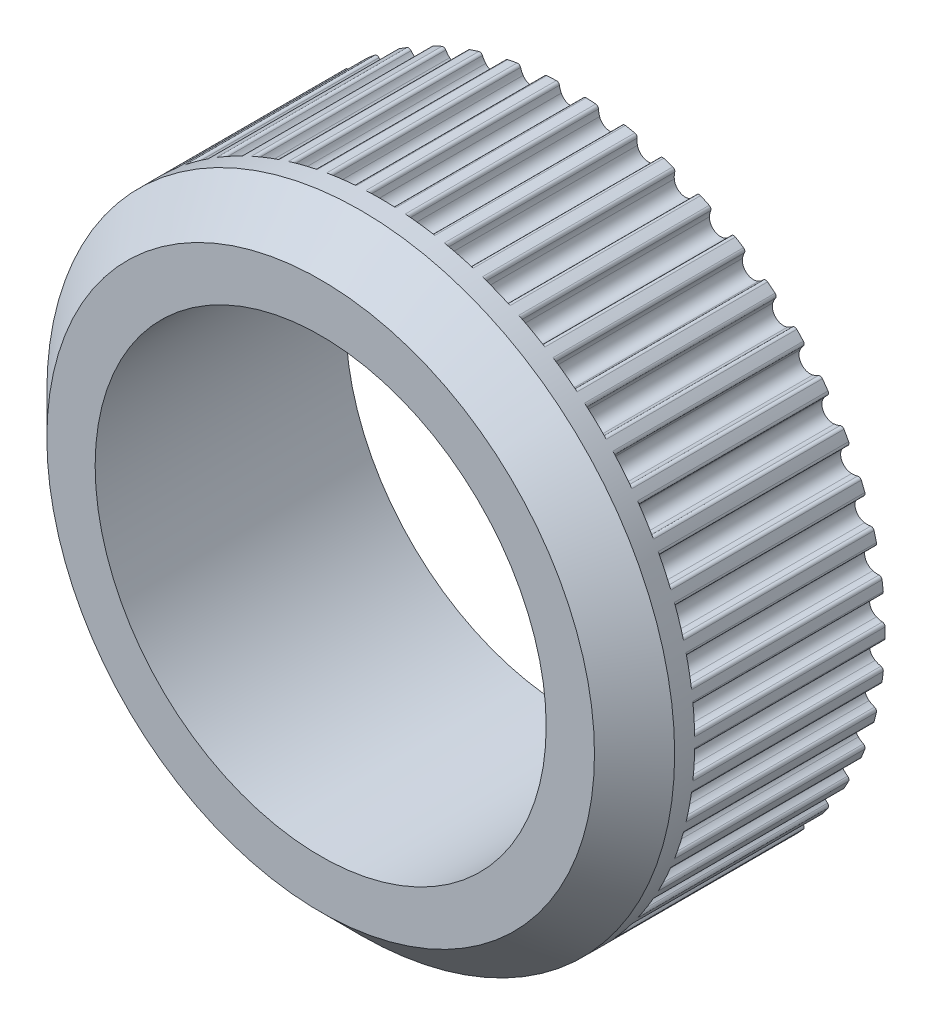
SolidWorks part; units mm, degrees
ref_plane "Front Plane" through (0, 0, 0) normal (0, 0, 1) x (1, 0, 0)
ref_plane "Top Plane" through (0, 0, 0) normal (0, 1, 0) x (1, 0, 0)
ref_plane "Right Plane" through (0, 0, 0) normal (1, 0, 0) x (0, 0, -1)
sketch "Sketch1" plane through (0, 0, 0) normal (0, 0, 1) x (1, 0, 0)
  line L1 (-1.885, 14.909) -> (1.885, 14.909) construction
  line L4 (0, 0) -> (0, 14.909) construction
  line L5 (0, 14.909) -> (0, 17.5781) construction
  line L6 (0, 15.913) -> (1.996, 15.7873) construction
  line L7 (1.996, 15.7873) -> (2.8744, 15.6763) construction
  line L8 (1.996, 15.7873) -> (1.885, 14.909) construction
  line L9 (-1.996, 15.7873) -> (-1.885, 14.909) construction
  line L10 (-1.9642, 15.5353) -> (-2.3604, 18.669)
  line L11 (-2.3604, 18.669) -> (2.3604, 18.669)
  line L12 (2.3604, 18.669) -> (1.9642, 15.5353)
  circle A0 centre (0, 0) radius 15.913 construction
  circle A1 centre (0, 0) radius 18.669 construction
  circle A2 centre (0, 0) radius 15.659 construction
  arc A3 (-0.4989, 15.2208) -> (0.4989, 15.2208) centre (0, 15.464) ccw
  arc A4 (-0.4989, 15.2208) -> (-0.5893, 15.5133) centre (0.4, 15.659) cw
  arc A5 (-1.9642, 15.5353) -> (-0.7449, 15.6413) centre (0, 0) cw
  arc A6 (-0.5893, 15.5133) -> (-0.7449, 15.6413) centre (-0.7377, 15.4914) ccw
  arc A7 (1.9642, 15.5353) -> (0.7449, 15.6413) centre (0, 0) ccw
  arc A8 (0.5893, 15.5133) -> (0.7449, 15.6413) centre (0.7377, 15.4914) cw
  arc A9 (0.4989, 15.2208) -> (0.5893, 15.5133) centre (-0.4, 15.659) ccw
  point P6 (0, 20.9083)
  point P11 (0, 15.913)
  point P13 (0, 18.669)
  point P14 (0, 15.659)
  dimension "D1" = 3.3302
  dimension "PD" = 31.826
  dimension "D2" = 1.6651
  dimension "OD" = 37.338
  dimension "R3" = 0.555
  dimension "R2" = 1
  dimension "R1" = 0.15
  dimension "b" = 0.4
  dimension "D3" = 2
  dimension "PLD" = 0.254
  dimension "h" = 0.75
sketch "Sketch2" plane through (0, 0, 0) normal (1, 0, 0) x (0, 0, -1)
  line L0 (-0.3687, 11.25) -> (9.1313, 11.25)
  line L3 (-0.3687, 11.25) -> (-0.3687, 18.669)
  line L4 (-0.3687, 18.669) -> (0.6963, 18.669) construction
  line L5 (0.6963, 18.669) -> (0.6963, 15.659) construction
  line L6 (0.6963, 15.659) -> (8.0663, 15.659)
  line L7 (8.0663, 15.659) -> (8.0663, 18.669) construction
  line L8 (8.0663, 18.669) -> (9.1313, 18.669) construction
  line L9 (9.1313, 18.669) -> (9.1313, 11.25)
  line L10 (-9.1313, 0) -> (9.1313, 0) construction
  line L11 (8.5988, 18.669) -> (8.0663, 17.164)
  line L12 (0.6963, 17.164) -> (0.1638, 18.669)
  line L13 (-0.3687, 18.669) -> (0.1638, 18.669)
  line L14 (0.6963, 17.164) -> (0.6963, 15.659)
  line L15 (8.0663, 15.659) -> (8.0663, 17.164)
  line L16 (8.5988, 18.669) -> (9.1313, 18.669)
  point P12 (0.6963, 17.164)
  point P14 (0.1638, 18.669)
  point P20 (8.0663, 17.164)
  point P21 (8.5988, 18.669)
  point P25 (8.0663, 0)
  point P26 (0.6963, 0)
  dimension "OA" = 18.2626
  dimension "Bore" = 22.5
  dimension "Outside Width" = 9.5
  dimension "Inside Width" = 7.37
revolve "Revolve1" add sketch "Sketch2" angle 360 mid plane about L10
sketch "Sketch3" plane through (0, 0, 0) normal (0, 0, 1) x (1, 0, 0)
  line L6 (2.3604, 18.669) -> (-2.3604, 18.669)
  line L7 (1.9642, 15.5353) -> (2.3604, 18.669)
  line L8 (-2.3604, 18.669) -> (-1.9642, 15.5353)
  line L9 (2.3604, 18.669) -> (-2.3604, 18.669)
  line L10 (1.9642, 15.5353) -> (2.3604, 18.669)
  line L11 (-2.3604, 18.669) -> (-1.9642, 15.5353)
  arc A8 (1.9642, 15.5353) -> (0.7449, 15.6413) centre (0, 0) ccw
  arc A9 (0.7449, 15.6413) -> (0.5893, 15.5133) centre (0.7377, 15.4914) ccw
  arc A10 (0.4989, 15.2208) -> (0.5893, 15.5133) centre (-0.4, 15.659) ccw
  arc A11 (-0.4989, 15.2208) -> (0.4989, 15.2208) centre (0, 15.464) ccw
  arc A12 (-0.5893, 15.5133) -> (-0.4989, 15.2208) centre (0.4, 15.659) ccw
  arc A13 (-0.5893, 15.5133) -> (-0.7449, 15.6413) centre (-0.7377, 15.4914) ccw
  arc A14 (-0.7449, 15.6413) -> (-1.9642, 15.5353) centre (0, 0) ccw
  arc A15 (1.9642, 15.5353) -> (0.7449, 15.6413) centre (0, 0) ccw
  arc A16 (0.7449, 15.6413) -> (0.5893, 15.5133) centre (0.7377, 15.4914) ccw
  arc A17 (0.4989, 15.2208) -> (0.5893, 15.5133) centre (-0.4, 15.659) ccw
  arc A18 (-0.4989, 15.2208) -> (0.4989, 15.2208) centre (0, 15.464) ccw
  arc A19 (-0.5893, 15.5133) -> (-0.4989, 15.2208) centre (0.4, 15.659) ccw
  arc A20 (-0.5893, 15.5133) -> (-0.7449, 15.6413) centre (-0.7377, 15.4914) ccw
  arc A21 (-0.7449, 15.6413) -> (-1.9642, 15.5353) centre (0, 0) ccw
  dimension "D1" = 0
extrude "Cut-Extrude1" cut sketch "Sketch3" against normal mid plane 20 from vertex starting at point (0, 15.659, -0.6963)
pattern_circular "CirPattern1" count 50 over 360 about axis through (0, 0, 9.1313) along (0, 0, 1) of "Cut-Extrude1"
sketch "Sketch4" plane through (0, 0, 0.3687) normal (0, 0, 1) x (1, 0, 0)
  circle A0 centre (0, 0) radius 15.659
  circle A1 centre (0, 0) radius 11.25
  circle A2 centre (0, 0) radius 11.25 construction
extrude "Boss-Extrude1" add sketch "Sketch4" along normal blind 3
ref_axis "Center Axis 1" through (0, 0, -9.1313) along (0, 0, 1)
ref_plane "Contact Plane 2" through (0, 0, -9.1313) normal (0, 0, -1) x (-1, 0, 0)
chamfer "Chamfer1" distance 2 angle 45 1 edges at (15.659, 0, 3.3687)
